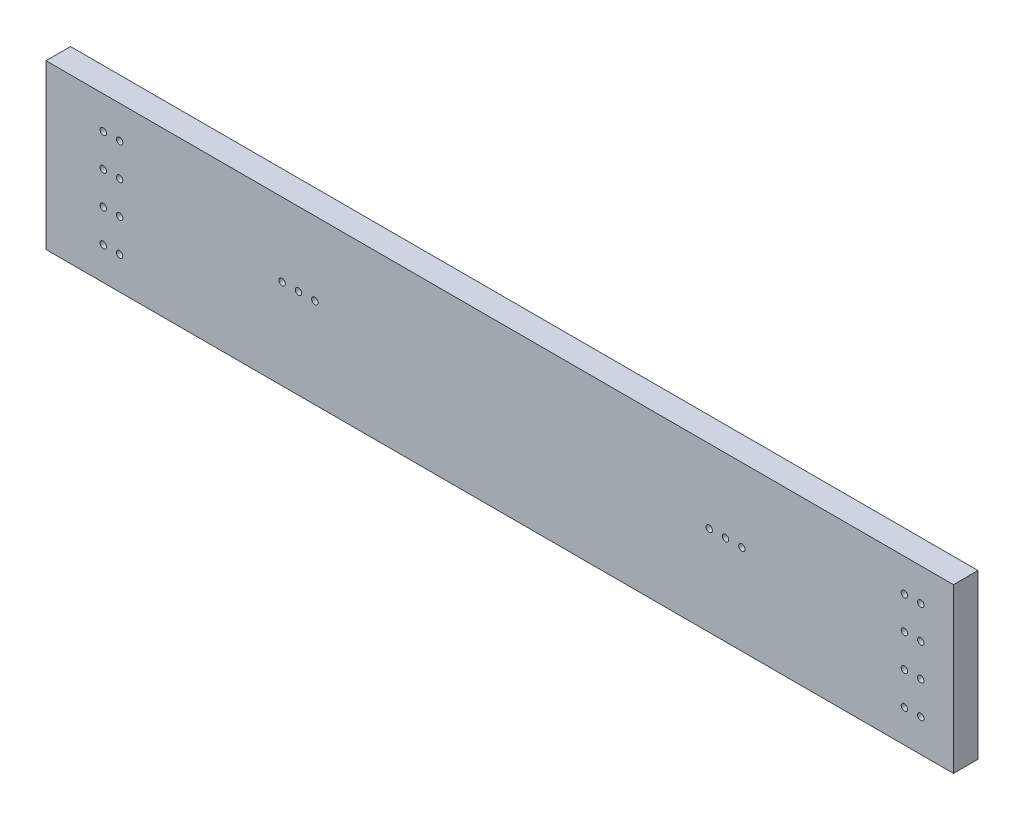
SolidWorks part; units mm, degrees
material "Pine"
ref_plane "Front Plane" through (0, 0, 0) normal (0, 0, 1) x (1, 0, 0)
ref_plane "Top Plane" through (0, 0, 0) normal (0, 1, 0) x (1, 0, 0)
ref_plane "Right Plane" through (0, 0, 0) normal (1, 0, 0) x (0, 0, -1)
sketch "robot, section, top of tube" plane through (0, 0, 0) normal (0, 1, 0) x (1, 0, 0)
  line L1 (-330.2, 0) -> (330.2, 0)
  line L2 (-330.2, 0) -> (-330.2, 660.4)
  line L3 (-330.2, 660.4) -> (330.2, 660.4)
  line L4 (330.2, 0) -> (330.2, 660.4)
  line L6 (146.05, 0) -> (146.05, 45.2974)
  line L7 (-146.05, 0) -> (-146.05, 45.2974)
  line L8 (0, 0) -> (0, 660.4) construction
  dimension "D1" = 660.4
  dimension "D3" = 184.15
sketch "robot approx side" plane through (0, 0, 0) normal (0, 0, 1) x (1, 0, 0)
  line L0 (-146.812, 0) -> (-146.812, 25.4)
  line L1 (-330.2, 0) -> (330.2, 0) construction
  line L2 (-146.812, 2.6416) -> (-121.9604, 2.6416)
  line L4 (0, 0) -> (0, 48.6273) construction
  line L5 (146.812, 2.6416) -> (121.9604, 2.6416)
  line L6 (146.812, 0) -> (146.812, 25.4)
  dimension "D1" = 2.6416
  dimension "D2" = 25.4
  dimension "D3" = 183.388
ref_plane "floor" through (0, -93.726, 0) normal (0, 1, 0) x (1, 0, 0)
ref_plane "bottom" through (0, -57.15, 0) normal (0, 1, 0) x (1, 0, 0)
ref_plane "top" through (0, 69.85, 0) normal (0, 1, 0) x (1, 0, 0)
sketch "Sketch4" plane through (0, 0, 0) normal (0, 1, 0) x (1, 0, 0)
  line L0 (-330.2, 0) -> (330.2, 0) construction
  line L1 (342.9, -12.7) -> (-361.95, -12.7)
  line L2 (342.9, -12.7) -> (342.9, -31.75)
  line L3 (342.9, -31.75) -> (-361.95, -31.75)
  line L4 (-361.95, -12.7) -> (-361.95, -31.75)
  line L5 (330.2, 0) -> (330.2, 660.4) construction
  line L6 (-330.2, 0) -> (-330.2, 660.4) construction
  dimension "D1" = 19.05
  dimension "D2" = 12.7
  dimension "D3" = 12.7
  dimension "D4" = 31.75
extrude "Boss-Extrude1" add sketch "Sketch4" along normal up to surface (69.85 mm away) from surface up to plane "top" starting at plane "bottom"
sketch "Sketch5" plane through (0, 0, 31.75) normal (0, 0, 1) x (1, 0, 0)
  line L0 (-9.525, 69.85) -> (-9.525, -57.15) construction
  line L1 (146.812, 0) -> (146.812, 25.4) construction
  line L2 (-361.95, 69.85) -> (-361.95, -57.15) construction
  line L4 (-361.95, 69.85) -> (342.9, 69.85) construction
  line L5 (-361.95, -57.15) -> (342.9, -57.15) construction
  line L6 (-361.95, 12.7) -> (342.9, 12.7) construction
  line L7 (342.9, 69.85) -> (342.9, -57.15) construction
  line L8 (-146.812, 0) -> (-146.812, 25.4) construction
  circle A0 centre (-317.5, 44.45) radius 2.4955
  circle A1 centre (-304.8, 44.45) radius 2.4955
  circle A2 centre (-317.5, 19.05) radius 2.4955
  circle A3 centre (-304.8, 19.05) radius 2.4955
  circle A4 centre (-317.5, -6.35) radius 2.4955
  circle A5 centre (-304.8, -6.35) radius 2.4955
  circle A6 centre (-317.5, -31.75) radius 2.4955
  circle A7 centre (-304.8, -31.75) radius 2.4955
  circle A14 centre (304.8, 44.45) radius 2.4955
  circle A15 centre (317.5, 44.45) radius 2.4955
  circle A16 centre (-178.562, 12.7) radius 2.4892
  circle A17 centre (-165.862, 12.7) radius 2.4892
  circle A18 centre (-153.162, 12.7) radius 2.4892
  circle A19 centre (153.162, 12.7) radius 2.4892
  circle A20 centre (165.862, 12.7) radius 2.4892
  circle A21 centre (178.562, 12.7) radius 2.4892
  circle A22 centre (317.5, 19.05) radius 2.4955
  circle A23 centre (304.8, 19.05) radius 2.4955
  circle A24 centre (317.5, -6.35) radius 2.4955
  circle A25 centre (304.8, -6.35) radius 2.4955
  circle A26 centre (317.5, -31.75) radius 2.4955
  circle A27 centre (304.8, -31.75) radius 2.4955
  point P30 (-146.812, 12.7)
  dimension "D3" = 4.9911
  dimension "D1" = 4.9784
  dimension "D9" = 12.7
  dimension "D10" = 6.35
  dimension "D11" = 6.35
  dimension "D12" = 12.7
  dimension "D13" = 12.7
  dimension "D16" = 25.4
  dimension "D2" = 12.7
  dimension "D4" = 25.4
  dimension "D5" = 44.45
  dimension "D7" = 25.4
  dimension "D8" = 12.7
  dimension "D14" = 25.4
  dimension "D15" = 12.7
  dimension "D18" = 25.4
  dimension "D6" = 4
  dimension "D17" = 4
extrude "Cut-Extrude1" cut sketch "Sketch5" against normal through all
equation "\"D3@Sketch4\"=\"D2@Sketch4\""
equation "\"D4@Sketch4\"=.75+\"D2@Sketch4\""
